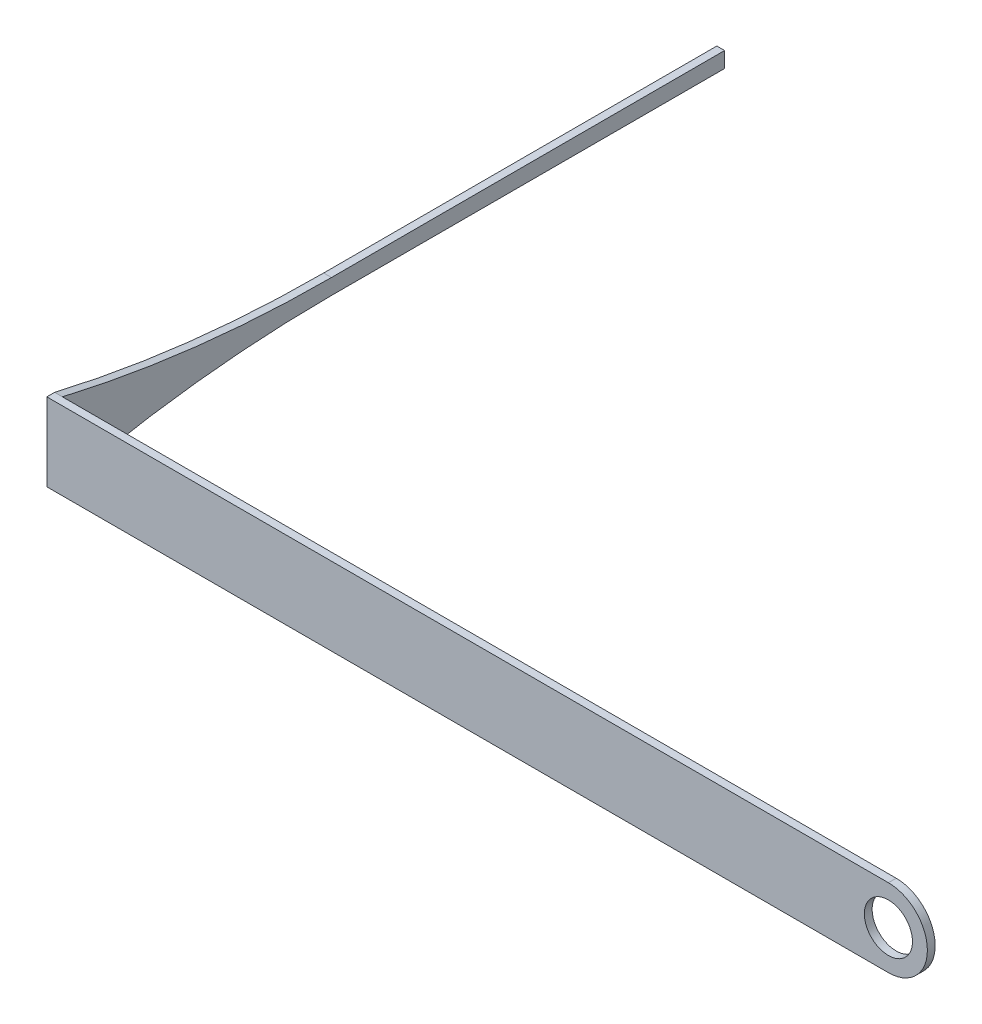
SolidWorks part; units mm, degrees
ref_plane "Front Plane" through (0, 0, 0) normal (0, 0, 1) x (1, 0, 0)
ref_plane "Top Plane" through (0, 0, 0) normal (0, 1, 0) x (1, 0, 0)
ref_plane "Right Plane" through (0, 0, 0) normal (1, 0, 0) x (0, 0, -1)
sketch "Sketch1" plane through (0, 0, 0) normal (0, 1, 0) x (1, 0, 0)
  line L0 (0, 0) -> (-107, 0)
  line L1 (-107, 0) -> (-107, 84.9819)
  line L2 (0, -1) -> (-108, -1)
  line L3 (-108, -1) -> (-108, 84.9819)
  line L4 (0, 0) -> (0, -1)
  line L5 (-108, 84.9819) -> (-107, 84.9819)
  dimension "D2" = 108
  dimension "D1" = 1
extrude "Boss-Extrude1" add sketch "Sketch1" along normal mid plane 10
sketch "Sketch2" plane through (0, 0, 1) normal (0, 0, 1) x (1, 0, 0)
  line L0 (-108, 5) -> (0, 5) construction
  circle A0 centre (0, 0) radius 3.0889
  circle A1 centre (0, 0) radius 5
extrude "Boss-Extrude2" add sketch "Sketch2" against normal up to surface (1 mm away) contours A1 A0 region at (-4.8586, 0, 1) up to face at (-53.5, 0, 0)
sketch "Sketch3" plane through (0, 0, 1) normal (0, 0, 1) x (1, 0, 0)
  circle A0 centre (0, 0) radius 3.0889
  arc A1 (0, -3.0889) -> (0, 3.0889) centre (0, 0) ccw construction
extrude "Cut-Extrude1" cut sketch "Sketch3" against normal up to surface (1 mm away) up to face at (-52.25, 0, 0)
ref_axis "Axis1" through (0, 0, 0) along (0, 0, 1)
sketch "Sketch4" plane through (-108, 0, 0) normal (-1, 0, 0) x (0, 0, 1)
  line L0 (-84.9819, -1) -> (-84.9819, 1)
  line L1 (-84.9819, 5) -> (-84.9819, -5) construction
  line L2 (-84.9819, 1) -> (-34.5274, 1)
  line L3 (-84.9819, -1) -> (-34.5274, -1)
  line L4 (-84.9819, 0) -> (-74.9325, 0) construction
  arc A0 (-34.5274, 1) -> (0, 5) centre (-34.5274, 152.0179) ccw
  arc A1 (-34.5274, -1) -> (0, -5) centre (-34.5274, -152.0179) cw
  point P5 (-84.9819, 0)
  line M7 (-84.9819, -5) -> (1, -5)
  line M9 (1, 5) -> (-84.9819, 5)
  line M10 (-84.9819, 5) -> (-84.9819, -5)
  dimension "D1" = 2
extrude "Cut-Extrude2" cut sketch "Sketch4" against normal blind 10 and the other way through all contours L2 A0 M9 M10 | A1 L3 M10 M7 region at (-108, 3.125, -47.7656) region at (-108, -3.125, -47.7656)
